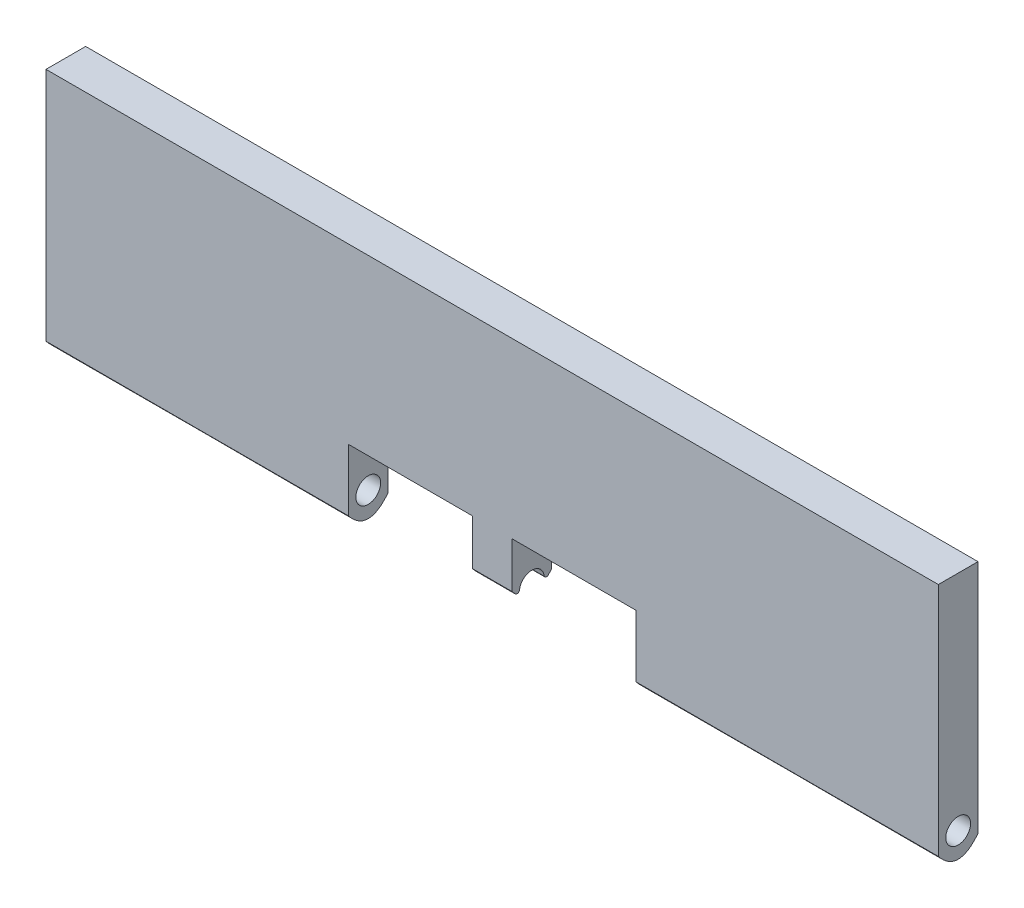
SolidWorks part; units mm, degrees
ref_plane "Plan de face" through (0, 0, 0) normal (0, 0, 1) x (1, 0, 0)
ref_plane "Plan de dessus" through (0, 0, 0) normal (0, 1, 0) x (1, 0, 0)
ref_plane "Plan de droite" through (0, 0, 0) normal (1, 0, 0) x (0, 0, -1)
sketch "Esquisse1" plane through (0, 0, 0) normal (0, 0, 1) x (1, 0, 0)
  line L0 (-29, -25) -> (-29, -10)
  line L1 (-90, -25) -> (-29, -25)
  line L2 (-90, -25) -> (-90, 25)
  line L3 (-90, 25) -> (90, 25)
  line L4 (90, -25) -> (90, 25)
  line L5 (-90, -25) -> (90, 25) construction
  line L6 (-90, 25) -> (90, -25) construction
  line L7 (-29, -10) -> (-4, -10)
  line L8 (-4, -10) -> (-4, -25)
  line L9 (0, 0) -> (0, -25) construction
  line L10 (-4, -25) -> (4, -25)
  line L11 (4, -10) -> (4, -25)
  line L12 (29, -10) -> (4, -10)
  line L13 (29, -25) -> (29, -10)
  line L14 (29, -25) -> (90, -25)
  point P0 (0, 0)
  dimension "D1" = 180
  dimension "D2" = 50
  dimension "D3" = 25
  dimension "D4" = 4
  dimension "D5" = 15
extrude "Boss.-Extru.1" add sketch "Esquisse1" along normal blind 8
sketch "Esquisse2" plane through (-90, 0, 0) normal (-1, 0, 0) x (0, 0, 1)
  line L0 (4, -25) -> (4, -8.5674) construction
  line L1 (8, -25) -> (0, -25) construction
  line L2 (4, -22.5) -> (0, -22.5) construction
  line L3 (0, 25) -> (0, -25) construction
  line L4 (8, 25) -> (8, -25) construction
  line L5 (0, -22.5) -> (0, -25)
  line L6 (0, -25) -> (8, -25)
  line L7 (8, -25) -> (8, -22.5)
  circle A0 centre (4, -20) radius 2.5
  spline S0 degree 2 poles (0, -22.5) (4, -27.5) (8, -22.5) knots 0 0 0 1 1 1
  line M1 (0, 25) -> (0, -25)
  line M2 (0, -25) -> (8, -25)
  line M3 (8, -25) -> (8, 25)
  dimension "D1" = 5
  dimension "D2" = 5
extrude "Enlèv. mat.-Extru.1" cut sketch "Esquisse2" against normal up to surface (180 mm away) contours S0 L6 M3 | S0 M1 M2 | A0 region at (-90, -24.25, 1) region at (-90, -24.25, 7) region at (-90, -20, 4) up to face at (90, 0, 4)
sketch "Esquisse4" plane through (0, 0, 0) normal (1, 0, 0) x (0, 0, -1)
  line L0 (0, 0) -> (5, 0) construction
  line L1 (5, 4.5) -> (0, 4.5)
  line L2 (0, 25) -> (0, -22.5) construction
  line L3 (5, -4.5) -> (0, -4.5)
  line L4 (0, 4.5) -> (0, -4.5)
  circle A0 centre (5, 0) radius 2.5
  arc A1 (5, -4.5) -> (5, 4.5) centre (5, 0) ccw
  dimension "D1" = 5
  dimension "D2" = 2
  dimension "D3" = 5
extrude "Boss.-Extru.2" add sketch "Esquisse4" along normal blind 2.5 and the other way blind 2.5
sketch "Esquisse6" plane through (-4, 0, 0) normal (-1, 0, 0) x (0, 0, 1)
  line L0 (1.6529, -20.8608) -> (6.3471, -20.8608) construction
  line L1 (8, -19.2216) -> (8, -22.5)
  line L2 (0, -19.2216) -> (0, -22.5)
  parabola Q0 (8, -22.5) -> (0, -22.5) focus (4, -23.4) apex (4, -25) construction
  parabola Q1 (0, -22.5) -> (8, -22.5) focus (4, -23.4) apex (4, -25) construction
  spline S1 degree 2 poles (0, -22.5) (4, -27.5) (8, -22.5) knots 0 0 0 1 1 1
  spline S2 degree 2 poles (0, -19.2216) (4, -24.2216) (8, -19.2216) knots 0 0 0 1 1 1
  point P0 (4, -20)
  point P19 (6.3471, -20.8608)
  point P20 (1.6529, -20.8608)
extrude "Enlèv. mat.-Extru.2" cut sketch "Esquisse6" against normal up to surface (8 mm away) up to face at (4, -22.5, 4)
fillet "Congé1" radius 0.5 2 edges at (0, -20.8608, 1.6529) (0, -20.8608, 6.3471)
